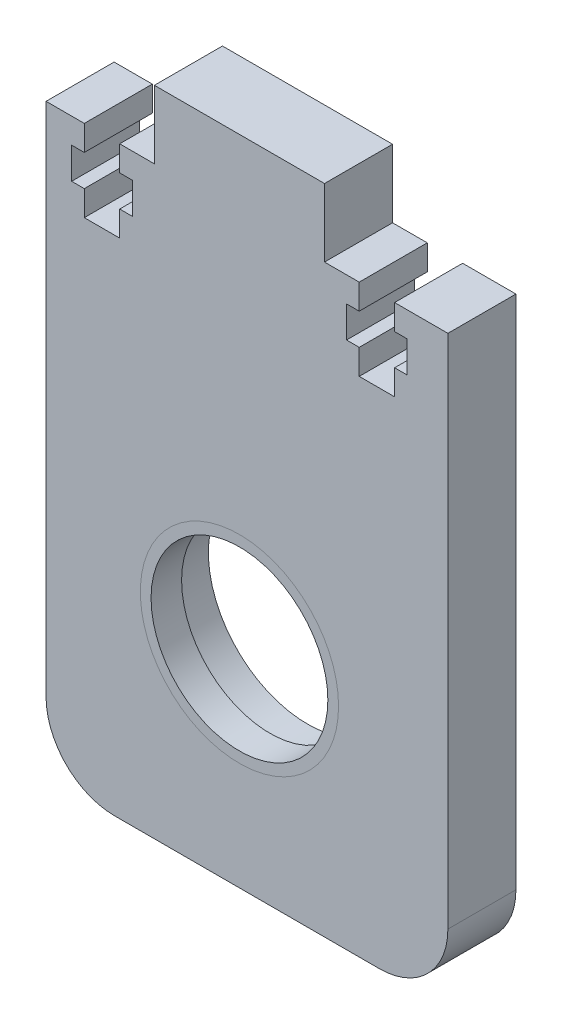
SolidWorks part; units mm, degrees
ref_plane "Front Plane" through (0, 0, 0) normal (0, 0, 1) x (1, 0, 0)
ref_plane "Top Plane" through (0, 0, 0) normal (0, 1, 0) x (1, 0, 0)
ref_plane "Right Plane" through (0, 0, 0) normal (1, 0, 0) x (0, 0, -1)
sketch "Sketch12" plane through (0, 0, 0) normal (0, 0, 1) x (1, 0, 0)
  line L0 (62.1258, 0) -> (62.1258, 109.1)
  line L1 (62.1258, 109.1) -> (137.1258, 109.1)
  line L2 (62.1258, 0) -> (137.1258, 0)
  line L3 (137.1258, 109.1) -> (137.1258, 0)
  circle A0 centre (99.6258, 37.5) radius 25.4
  circle A1 centre (99.6258, 37.5) radius 6.5
  dimension "D3" = 50.8
  dimension "D4" = 13
  dimension "D1" = 109.1
  dimension "D2" = 75
extrude "Boss-Extrude10" add sketch "Sketch12" along normal blind 12.7 separate body contours L1 L3 L2 L0
sketch "Sketch15" plane through (0, 0, 12.7) normal (0, 0, 1) x (1, 0, 0)
  circle A0 centre (98.2196, 38.6276) radius 25.4
  dimension "D1" = 50.8
sketch "Sketch24" plane through (0, 0, 12.7) normal (0, 0, 1) x (1, 0, 0)
  line L0 (62.1258, 109.1) -> (62.1258, 105.1)
  line L1 (62.1258, 0) -> (62.1258, 109.1) construction
  line L2 (62.1258, 105.1) -> (137.1258, 105.1)
  line L3 (137.1258, 109.1) -> (137.1258, 0) construction
  line L4 (137.1258, 105.1) -> (137.1258, 109.1)
  line L5 (137.1258, 109.1) -> (62.1258, 109.1)
  dimension "D1" = 4
sketch "Sketch25" plane through (0, 0, 12.7) normal (0, 0, 1) x (1, 0, 0)
  circle A0 centre (98.2196, 38.6276) radius 18.5
  dimension "D1" = 37
extrude "Cut-Extrude1" cut sketch "Sketch25" against normal through all
sketch "Sketch26" plane through (0, 0, 12.7) normal (0, 0, 1) x (1, 0, 0)
  circle A0 centre (98.2196, 38.6276) radius 16.5
  circle A1 centre (98.2196, 38.6276) radius 18.5
  dimension "D1" = 37
  dimension "D2" = 2
extrude "Boss-Extrude15" add sketch "Sketch26" against normal blind 5.7 separate body
fillet "Fillet1" radius 12.8 2 edges at (137.1258, 0, 6.35) (62.1258, 0, 6.35)
sketch "Sketch27" plane through (0, 0, 0) normal (0, 0, -1) x (-1, 0, 0)
  line L0 (-69.2616, 109.1) -> (-69.2616, 104.401)
  line L1 (-137.1258, 109.1) -> (-62.1258, 109.1) construction
  line L2 (-69.2616, 104.401) -> (-66.8996, 104.401)
  line L3 (-66.8996, 104.401) -> (-66.8996, 98.559)
  line L4 (-66.8996, 98.559) -> (-69.2616, 98.559)
  line L5 (-69.2616, 98.559) -> (-69.2616, 93.86)
  line L6 (-69.2616, 93.86) -> (-75.8656, 93.86)
  line L7 (-75.8656, 93.86) -> (-75.8656, 98.559)
  line L8 (-75.8656, 98.559) -> (-78.2276, 98.559)
  line L9 (-78.2276, 98.559) -> (-78.2276, 104.401)
  line L10 (-78.2276, 104.401) -> (-75.8656, 104.401)
  line L11 (-75.8656, 104.401) -> (-75.8656, 109.1)
  line L12 (-75.8656, 109.1) -> (-69.2616, 109.1)
  line L14 (-98.2196, 38.6276) -> (-98.2196, 109.1) construction
  line L16 (-120.5737, 104.401) -> (-120.5737, 109.1)
  line L17 (-118.2117, 104.401) -> (-120.5737, 104.401)
  line L18 (-118.2117, 98.559) -> (-118.2117, 104.401)
  line L19 (-120.5737, 98.559) -> (-118.2117, 98.559)
  line L20 (-120.5737, 93.86) -> (-120.5737, 98.559)
  line L21 (-127.1777, 93.86) -> (-120.5737, 93.86)
  line L22 (-127.1777, 98.559) -> (-127.1777, 93.86)
  line L23 (-129.5397, 98.559) -> (-127.1777, 98.559)
  line L24 (-129.5397, 104.401) -> (-129.5397, 98.559)
  line L25 (-127.1777, 104.401) -> (-129.5397, 104.401)
  line L26 (-127.1777, 109.1) -> (-127.1777, 104.401)
  line L27 (-120.5737, 109.1) -> (-127.1777, 109.1)
  dimension "D1" = 6.604
  dimension "D2" = 11.328
  dimension "D3" = 5.842
  dimension "D4" = 15.24
ref_axis "Axis1" through (98.2196, 38.6276, 0) along (0, 1, 0)
extrude "Cut-Extrude2" cut sketch "Sketch27" against normal through all
sketch "Sketch28" plane through (0, 109.1, 0) normal (0, 1, 0) x (1, 0, 0)
  line L0 (98.2196, 0) -> (82.3446, 0)
  line L1 (75.8656, 0) -> (120.5737, 0) construction
  line L2 (82.3446, 0) -> (82.3446, -12.7)
  line L3 (82.3446, -12.7) -> (114.0946, -12.7)
  line L4 (114.0946, -12.7) -> (114.0946, 0)
  line L5 (114.0946, 0) -> (98.2196, 0)
  line L6 (72.8196, -12.7) -> (123.6196, -12.7) construction
  point P4 (0, 0)
  point P8 (0, 0)
  point P9 (103.9991, -12.7)
  dimension "D1" = 31.75
extrude "Boss-Extrude16" add sketch "Sketch28" along normal blind 12.7
